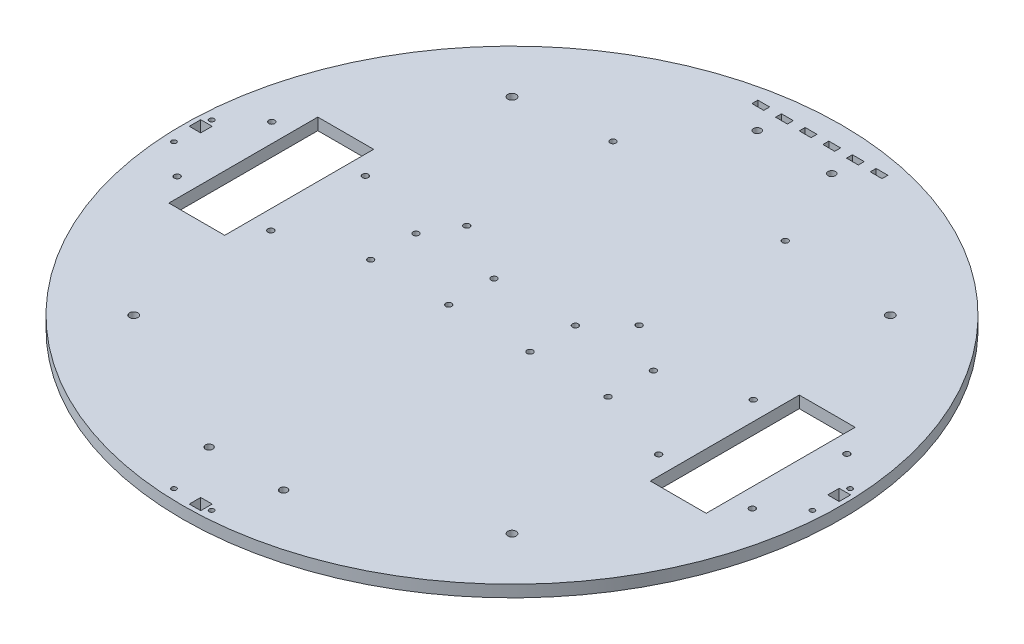
SolidWorks part; units mm, degrees
ref_plane "Front Plane" through (0, 0, 0) normal (0, 0, 1) x (1, 0, 0)
ref_plane "Top Plane" through (0, 0, 0) normal (0, 1, 0) x (1, 0, 0)
ref_plane "Right Plane" through (0, 0, 0) normal (1, 0, 0) x (0, 0, -1)
sketch "Sketch1" plane through (0, 0, 0) normal (0, 1, 0) x (1, 0, 0)
  line L0 (168.375, 7.335) -> (174.525, 7.335)
  line L1 (-144.3, 40) -> (-114.3, 40)
  line L2 (-144.3, 40) -> (-144.3, -40)
  line L3 (-144.3, -40) -> (-114.3, -40)
  line L4 (-114.3, 40) -> (-114.3, -40)
  line L13 (114.3, 40) -> (144.3, 40)
  line L14 (114.3, 40) -> (114.3, -40)
  line L15 (114.3, -40) -> (144.3, -40)
  line L16 (144.3, 40) -> (144.3, -40)
  line L17 (1.185, -168.375) -> (7.335, -168.375)
  line L18 (1.185, -168.375) -> (1.185, -174.525)
  line L19 (1.185, -174.525) -> (7.335, -174.525)
  line L20 (7.335, -168.375) -> (7.335, -174.525)
  line L21 (168.375, 7.335) -> (168.375, 1.185)
  line L22 (168.375, 1.185) -> (174.525, 1.185)
  line L23 (174.525, 7.335) -> (174.525, 1.185)
  line L24 (-174.525, 7.335) -> (-168.375, 7.335)
  line L25 (-174.525, 7.335) -> (-174.525, 1.185)
  line L26 (-174.525, 1.185) -> (-168.375, 1.185)
  line L27 (-168.375, 7.335) -> (-168.375, 1.185)
  line L28 (-21.295, 162.8645) -> (-14.945, 162.8645)
  line L29 (-33.995, 166.0395) -> (-27.645, 166.0395)
  line L30 (-33.995, 166.0395) -> (-33.995, 162.8645)
  line L31 (-33.995, 162.8645) -> (-27.645, 162.8645)
  line L32 (-27.645, 166.0395) -> (-27.645, 162.8645)
  line L33 (-14.945, 166.0395) -> (-14.945, 162.8645)
  line L34 (-21.295, 166.0395) -> (-14.945, 166.0395)
  line L35 (-21.295, 166.0395) -> (-21.295, 162.8645)
  line L36 (-8.595, 162.8645) -> (-2.245, 162.8645)
  line L37 (-2.245, 166.0395) -> (-2.245, 162.8645)
  line L38 (-8.595, 166.0395) -> (-2.245, 166.0395)
  line L39 (-8.595, 166.0395) -> (-8.595, 162.8645)
  line L40 (4.105, 162.8645) -> (10.455, 162.8645)
  line L41 (10.455, 166.0395) -> (10.455, 162.8645)
  line L42 (4.105, 166.0395) -> (10.455, 166.0395)
  line L43 (4.105, 166.0395) -> (4.105, 162.8645)
  line L44 (16.805, 162.8645) -> (23.155, 162.8645)
  line L45 (23.155, 166.0395) -> (23.155, 162.8645)
  line L46 (16.805, 166.0395) -> (23.155, 166.0395)
  line L47 (16.805, 166.0395) -> (16.805, 162.8645)
  line L48 (29.505, 162.8645) -> (35.855, 162.8645)
  line L49 (35.855, 166.0395) -> (35.855, 162.8645)
  line L50 (29.505, 166.0395) -> (35.855, 166.0395)
  line L51 (29.505, 166.0395) -> (29.505, 162.8645)
  circle A0 centre (0, 0) radius 177
  circle A1 centre (-154.46, 25.4) radius 1.6
  circle A2 centre (-154.46, -25.4) radius 1.6
  circle A3 centre (154.46, 25.4) radius 1.6
  circle A4 centre (154.46, -25.4) radius 1.6
  circle A5 centre (-104.14, 25.4) radius 1.6
  circle A6 centre (-104.14, -25.4) radius 1.6
  circle A7 centre (104.14, 25.4) radius 1.6
  circle A8 centre (104.14, -25.4) radius 1.6
  circle A9 centre (-53.7, 107.95) radius 1.6
  circle A10 centre (38.8, 107.95) radius 1.6
  circle A11 centre (-53.7, 29.45) radius 1.6
  circle A12 centre (38.8, 29.45) radius 1.6
  circle A13 centre (-101.6, -101.6) radius 2.2479
  circle A14 centre (101.6, -101.6) radius 2.2479
  circle A15 centre (-101.6, 101.6) radius 2.2479
  circle A16 centre (101.6, 101.6) radius 2.2479
  circle A17 centre (-20, -142.687) radius 2
  circle A18 centre (20, -142.687) radius 2
  circle A19 centre (-20, 151.7193) radius 2
  circle A20 centre (20, 151.7193) radius 2
  circle A21 centre (-10.125, -171.45) radius 1.3
  circle A22 centre (10.125, -171.45) radius 1.3
  circle A23 centre (171.45, -10.125) radius 1.3
  circle A24 centre (171.45, 10.125) radius 1.3
  circle A25 centre (-171.45, -10.125) radius 1.3
  circle A26 centre (-171.45, 10.125) radius 1.3
  circle A27 centre (-63.76, 12.204) radius 1.6
  circle A28 centre (-63.76, -12.18) radius 1.6
  circle A29 centre (-21.85, 12.204) radius 1.6
  circle A30 centre (-21.85, -12.18) radius 1.6
  circle A31 centre (63.76, -12.18) radius 1.6
  circle A32 centre (21.85, -12.18) radius 1.6
  circle A33 centre (21.85, 12.204) radius 1.6
  circle A34 centre (63.76, 12.204) radius 1.6
  point P9 (-114.3, 0)
  point P10 (-0.9618, 0)
  point P11 (-0.9618, 0)
  point P14 (114.3, 0)
  point P26 (-144.3, 0)
  point P27 (144.3, 0)
  dimension "D1" = 354
  dimension "D10" = 3.2
  dimension "D12" = 10.16
  dimension "D13" = 3.2
  dimension "D16" = 10.16
  dimension "D17" = 50.8
  dimension "D20" = 3.2
  dimension "D22" = 3.2
  dimension "D23" = 10.16
  dimension "D24" = 50.8
  dimension "D25" = 25.4
  dimension "D26" = 3.2
  dimension "D27" = 3.2
  dimension "D32" = 3.2
  dimension "D33" = 3.2
  dimension "D34" = 3.2
  dimension "D35" = 3.2
  dimension "D44" = 4.4958
  dimension "D45" = 4.4958
  dimension "D46" = 4.4958
  dimension "D47" = 4.4958
  dimension "D55" = 4
  dimension "D56" = 4
  dimension "D59" = 20
  dimension "D60" = 4
  dimension "D61" = 4
  dimension "D62" = 0
  dimension "D63" = 40
  dimension "D64" = 20
  dimension "D65" = 2.6
  dimension "D66" = 2.6
  dimension "D74" = 171.45
  dimension "D75" = 2.6
  dimension "D76" = 2.6
  dimension "D77" = 0
  dimension "D87" = 2.6
  dimension "D88" = 2.6
  dimension "D90" = 2.79
  dimension "D92" = 0
  dimension "D98" = 3.2
  dimension "D99" = 3.2
  dimension "D100" = 3.2
  dimension "D101" = 3.2
  dimension "D102" = 24.384
  dimension "D103" = 24.384
  dimension "D104" = 41.91
  dimension "D105" = 41.91
  dimension "D106" = 0
  dimension "D110" = 3.2
  dimension "D111" = 3.2
  dimension "D112" = 3.2
  dimension "D113" = 3.2
  dimension "D115" = 41.91
  dimension "D117" = 24.384
  dimension "D119" = 24.384
  dimension "D122" = 3.2
  dimension "D123" = 3.2
  dimension "D2" = 30
  dimension "D3" = 80
  dimension "D4" = 0
  dimension "D5" = 114.3
  dimension "D6" = 30
  dimension "D7" = 80
  dimension "D8" = 0
  dimension "D9" = 114.3
  dimension "D11" = 50.8
  dimension "D14" = 10.16
  dimension "D15" = 25.4
  dimension "D18" = 25.4
  dimension "D19" = 10.16
  dimension "D21" = 10.16
  dimension "D28" = 50.8
  dimension "D29" = 10.16
  dimension "D30" = 10.16
  dimension "D31" = 25.4
  dimension "D36" = 78.5
  dimension "D37" = 78.5
  dimension "D38" = 92.5
  dimension "D39" = 92.5
  dimension "D40" = 0
  dimension "D41" = 0
  dimension "D42" = 38.8
  dimension "D43" = 107.95
  dimension "D48" = 203.2
  dimension "D49" = 203.2
  dimension "D50" = 203.2
  dimension "D51" = 203.2
  dimension "D52" = 0
  dimension "D53" = 101.6
  dimension "D54" = 101.6
  dimension "D57" = 40
  dimension "D58" = 0
  dimension "D67" = 0
  dimension "D68" = 20.25
  dimension "D69" = 10.125
  dimension "D70" = 6.15
  dimension "D71" = 6.15
  dimension "D72" = 2.79
  dimension "D73" = 3.075
  dimension "D78" = 20.25
  dimension "D79" = 10.125
  dimension "D80" = 6.15
  dimension "D81" = 6.15
  dimension "D82" = 2.79
  dimension "D83" = 3.075
  dimension "D84" = 171.45
  dimension "D85" = 6.15
  dimension "D86" = 6.15
  dimension "D89" = 20.25
  dimension "D91" = 3.075
  dimension "D93" = 171.45
  dimension "D94" = 10.125
  dimension "D95" = 3.175
  dimension "D96" = 6.35
  dimension "D107" = 0
  dimension "D108" = 50.54
  dimension "D109" = 27.82
  dimension "D114" = 0
  dimension "D116" = 0
  dimension "D118" = 41.91
  dimension "D120" = 50.54
  dimension "D121" = 27.82
  dimension "D97" = 6
extrude "Boss-Extrude1" add sketch "Sketch1" along normal blind 6.35
